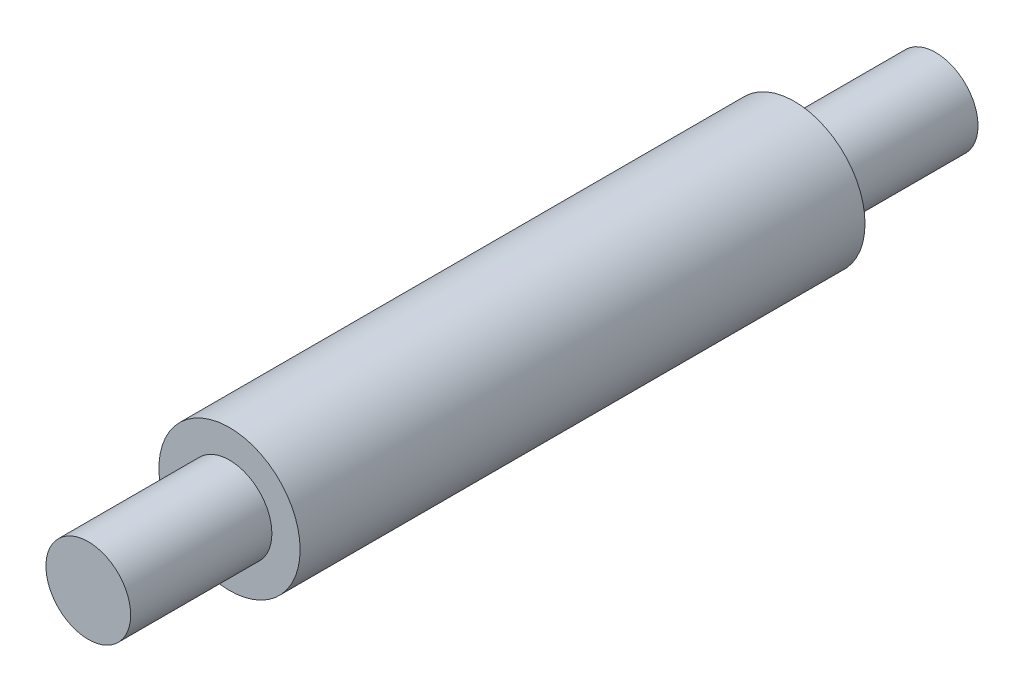
SolidWorks part; units mm, degrees
ref_plane "Front Plane" through (0, 0, 0) normal (0, 0, 1) x (1, 0, 0)
ref_plane "Top Plane" through (0, 0, 0) normal (0, 1, 0) x (1, 0, 0)
ref_plane "Right Plane" through (0, 0, 0) normal (1, 0, 0) x (0, 0, -1)
sketch "Sketch1" plane through (0, 0, 0) normal (0, 0, 1) x (1, 0, 0)
  circle A0 centre (0, 0) radius 5
  dimension "D1" = 10
extrude "Boss-Extrude1" add sketch "Sketch1" along normal blind 20 and the other way blind 20
sketch "Sketch2" plane through (0, 0, 20) normal (0, 0, 1) x (1, 0, 0)
  circle A0 centre (0, 0) radius 3
  dimension "D1" = 6
extrude "Boss-Extrude2" add sketch "Sketch2" along normal blind 10
mirror "Mirror1" about plane through (0, 0, 0) normal (0, 0, 1) of "Boss-Extrude2"
